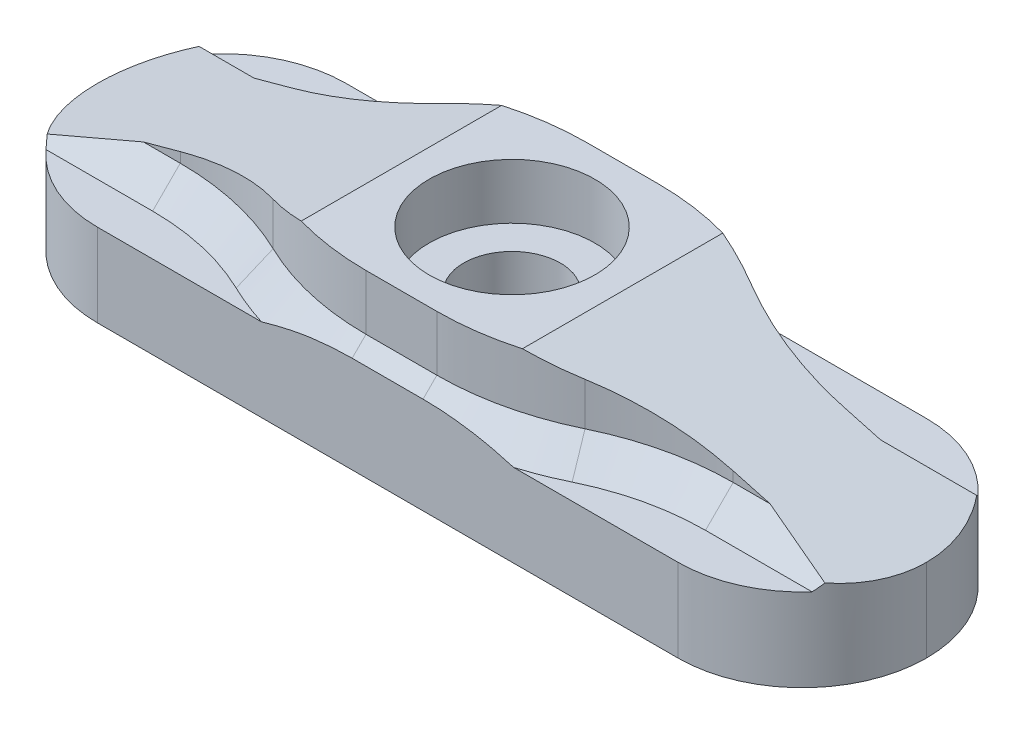
SolidWorks part; units mm, degrees
material "ABS"
ref_plane "Front Plane" through (0, 0, 0) normal (0, 0, 1) x (1, 0, 0)
ref_plane "Top Plane" through (0, 0, 0) normal (0, 1, 0) x (1, 0, 0)
ref_plane "Right Plane" through (0, 0, 0) normal (1, 0, 0) x (0, 0, -1)
sketch "Sketch1" plane through (0, 0, 0) normal (0, 1, 0) x (1, 0, 0)
  line L1 (-15, -4.5) -> (15, -4.5)
  line L2 (-15, -4.5) -> (-15, 4.5)
  line L3 (-15, 4.5) -> (15, 4.5)
  line L4 (15, -4.5) -> (15, 4.5)
  line L5 (-15, -4.5) -> (15, 4.5) construction
  line L6 (-15, 4.5) -> (15, -4.5) construction
  point P0 (0, 0)
  dimension "D1" = 9
  dimension "D2" = 30
extrude "Boss-Extrude1" add sketch "Sketch1" along normal blind 3
sketch "Sketch2" plane through (0, 0, 0) normal (0, 0, 1) x (1, 0, 0)
  line L0 (-15, 3) -> (-4, 6)
  line L1 (-4, 6) -> (4, 6)
  line L2 (4, 6) -> (15, 3)
  line L3 (15, 3) -> (-15, 3)
  point P3 (0, 6)
  dimension "D1" = 3
  dimension "D2" = 8
extrude "Boss-Extrude2" add sketch "Sketch2" along normal blind 4 and the other way blind 4
sketch "Sketch3" plane through (0, 6, 0) normal (0, 1, 0) x (1, 0, 0)
  line L0 (-15, 4) -> (-15, -4) construction
  line L1 (-4, -4) -> (4, -4)
  line L2 (-4, -4) -> (-4, 4)
  line L3 (-4, 4) -> (4, 4)
  line L4 (4, -4) -> (4, 4)
  line L5 (-4, -4) -> (4, 4) construction
  line L6 (-4, 4) -> (4, -4) construction
  line L7 (15, 4) -> (-15, 4)
  line L8 (15, 4) -> (15, 2)
  line L9 (15, 2) -> (-15, 2)
  line L10 (-15, 4) -> (-15, 2)
  line L11 (15, 4) -> (15, -4) construction
  line L12 (-15, -4) -> (15, -4)
  line L13 (-15, -4) -> (-15, -2)
  line L14 (-15, -2) -> (15, -2)
  line L15 (15, -4) -> (15, -2)
  point P0 (0, 0)
  point P21 (0, 0)
  line M9 (-4, 4) -> (-4, -4)
  line M11 (4, -4) -> (4, 4)
  dimension "D1" = 4
extrude "Cut-Extrude1" cut sketch "Sketch3" against normal up to surface (3 mm away) contours L9 L8 L7 L4 | L7 L10 L9 M9 | L14 L13 L12 M9 | L12 L15 L14 M11 region at (-9.5, 6, 3) region at (9.5, 6, 3) region at (-9.5, 6, -3) region at (9.5, 6, -3) up to face at (0, 3, 4.25)
sketch "Sketch5" plane through (0, 6, 0) normal (0, 1, 0) x (1, 0, 0)
  circle A0 centre (0, 0) radius 1.75
  dimension "D1" = 3.5
extrude "Cut-Extrude2" cut sketch "Sketch5" against normal blind 14
sketch "Sketch6" plane through (0, 6, 0) normal (0, 1, 0) x (1, 0, 0)
  circle A0 centre (0, 0) radius 3
  dimension "D1" = 6
extrude "Cut-Extrude3" cut sketch "Sketch6" against normal blind 2
fillet "Fillet1" radius 10 4 edges at (-4, 4.5, -2) (4, 4.5, -2) (4, 4.5, 2) (-4, 4.5, 2)
fillet "Fillet2" radius 10 4 edges at (-4, 4.5, -4) (4, 4.5, -4) (4, 4.5, 4) (-4, 4.5, 4)
chamfer "Chamfer1" distance 1 angle 45 14 edges at (12.5, 3, -2) (7.7639, 3, -2.2532) (-12.5, 3, -2) (3.5183, 3, -3.7468) (-7.7639, 3, -2.2532) (0, 3, -4) (-3.5183, 3, -3.7468) (12.5, 3, 2) (7.7639, 3, 2.2532) (3.5183, 3, 3.7468) (0, 3, 4) (-3.5183, 3, 3.7468) (-12.5, 3, 2) (-7.7639, 3, 2.2532)
fillet "Fillet3" radius 4.5 4 edges at (15, 1.5, -4.5) (15, 1.5, 4.5) (-15, 1.5, 4.5) (-15, 1.5, -4.5)
